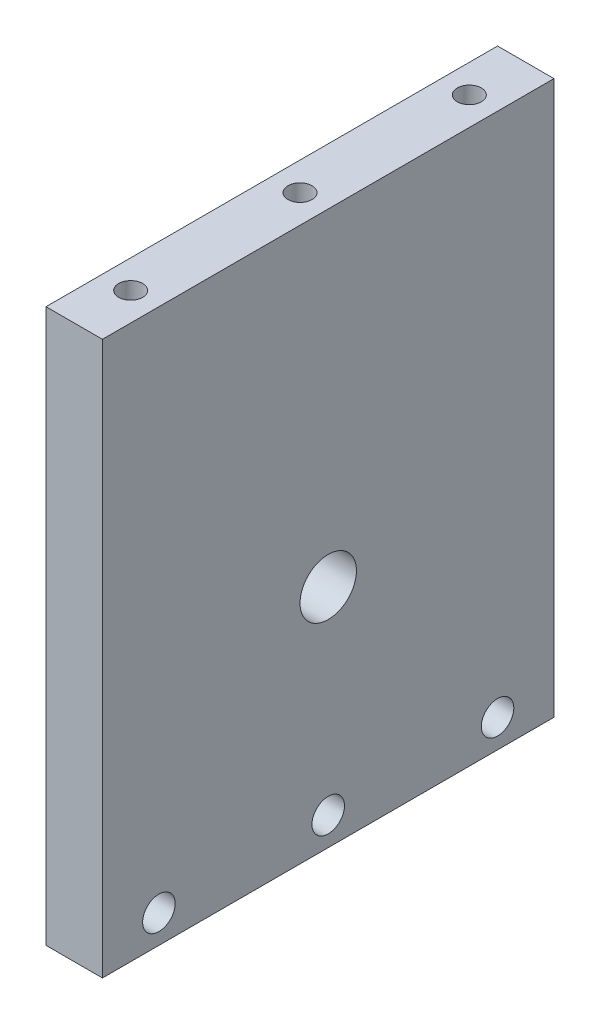
SolidWorks part; units mm, degrees
ref_plane "Front Plane" through (0, 0, 0) normal (0, 0, 1) x (1, 0, 0)
ref_plane "Top Plane" through (0, 0, 0) normal (0, 1, 0) x (1, 0, 0)
ref_plane "Right Plane" through (0, 0, 0) normal (1, 0, 0) x (0, 0, -1)
sketch "Sketch1" plane through (0, 0, 0) normal (1, 0, 0) x (0, 0, -1)
  line L1 (0, 0) -> (-50.8, 0)
  line L2 (0, 0) -> (0, 62.23)
  line L3 (0, 62.23) -> (-50.8, 62.23)
  line L4 (-50.8, 0) -> (-50.8, 62.23)
  dimension "D1" = 62.23
  dimension "D2" = 50.8
extrude "Boss-Extrude1" add sketch "Sketch1" along normal blind 6.35
sketch "Sketch2" plane through (0, 62.23, 0) normal (0, 1, 0) x (1, 0, 0)
  line L0 (0, 0) -> (0, -50.8) construction
  line L1 (6.35, -50.8) -> (0, -50.8) construction
  circle A0 centre (3.175, -44.45) radius 1.7526
  circle A1 centre (3.175, -6.35) radius 1.7526
  circle A3 centre (3.175, -25.4) radius 1.7526
  dimension "D1" = 3.5052
  dimension "D3" = 3.5052
  dimension "D5" = 3.5052
  dimension "D2" = 3.175
  dimension "D4" = 6.35
  dimension "D6" = 25.4
  dimension "D7" = 44.45
sketch "Sketch3" plane through (6.35, 0, 0) normal (1, 0, 0) x (0, 0, -1)
  line L0 (-50.8, 62.23) -> (-50.8, 0) construction
  line L1 (-50.8, 0) -> (0, 0) construction
  circle A0 centre (-44.45, 3.175) radius 1.8288
  circle A1 centre (-25.4, 3.175) radius 1.8288
  circle A2 centre (-6.35, 3.175) radius 1.8288
  dimension "D7" = 3.6576
  dimension "D8" = 3.6576
  dimension "D9" = 3.6576
  dimension "D1" = 6.35
  dimension "D2" = 25.4
  dimension "D3" = 44.45
  dimension "D4" = 3.175
  dimension "D5" = 3.175
  dimension "D6" = 3.175
extrude "Cut-Extrude1" cut sketch "Sketch3" against normal blind 6.35
hole_wizard "#6-32 Tapped Hole1" positions "Sketch10" profile "Sketch11" tap size "#6-32" standard "ANSI Inch"
sketch "Sketch10" plane through (0, 62.23, 0) normal (0, 1, 0) x (1, 0, 0)
  point P0 (3.175, -6.35)
  point P3 (3.175, -25.4)
  point P6 (3.175, -44.45)
sketch "Sketch11" plane through (3.175, 62.23, 6.35) normal (1, 0, 0) x (0, 0, 1)
  line L0 (0, 0) -> (0, 12.7)
  line L1 (0, 12.7) -> (1.3525, 11.8873)
  line L2 (1.3525, 11.8873) -> (1.3525, 0)
  line L5 (1.3525, 0) -> (0, 0)
  line L10 (0, 12.7) -> (-1.3526, 11.8873) construction
  line L11 (0, -6.35) -> (0, 107.95) construction
  dimension "Tap Drill Dia." = 2.7051
  dimension "Tap Drill Depth" = 12.7
  dimension "Drill Angle" = 118
cosmetic thread "Hole Thread1"
cosmetic thread "Hole Thread2"
cosmetic thread "Hole Thread3"
sketch "Sketch12" plane through (6.35, 0, 0) normal (1, 0, 0) x (0, 0, -1)
  line L0 (-50.8, 0) -> (0, 0) construction
  line L1 (-50.8, 62.23) -> (-50.8, 0) construction
  circle A0 centre (-25.4, 25.4) radius 3.175
  dimension "D1" = 6.35
  dimension "D2" = 25.4
  dimension "D3" = 25.4
extrude "Cut-Extrude3" cut sketch "Sketch12" against normal blind 6.35
